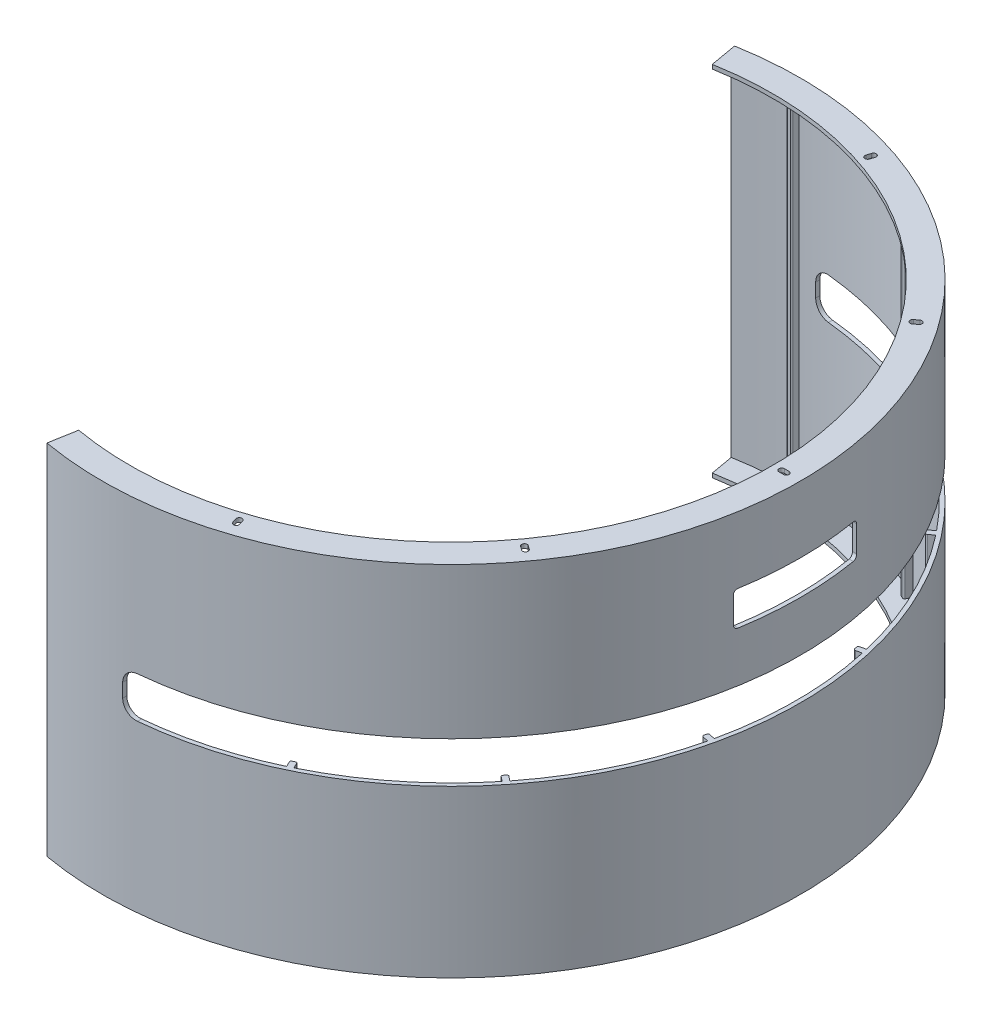
SolidWorks part; units mm, degrees
ref_plane "Front Plane" through (0, 0, 0) normal (0, 0, 1) x (1, 0, 0)
ref_plane "Top Plane" through (0, 0, 0) normal (0, 1, 0) x (1, 0, 0)
ref_plane "Right Plane" through (0, 0, 0) normal (1, 0, 0) x (0, 0, -1)
sketch "Sketch3" plane through (0, 0, 0) normal (0, 1, 0) x (1, 0, 0)
  line L0 (0, -251.5) -> (0, 251.5)
  line L1 (-44.1935, 250.6336) -> (-43.6725, 247.6791)
  line L2 (-43.6725, -247.6791) -> (-44.1935, -250.6336)
  arc A0 (0, 251.5) -> (0, -251.5) centre (0, 0) cw
  arc A1 (0, 251.5) -> (-43.6725, 247.6791) centre (0, 0) ccw
  arc A2 (0, -251.5) -> (-43.6725, -247.6791) centre (0, 0) cw
  arc A3 (0, 254.5) -> (0, -254.5) centre (0, 0) cw
  arc A4 (0, 254.5) -> (-44.1935, 250.6336) centre (0, 0) ccw
  arc A5 (0, -254.5) -> (-44.1935, -250.6336) centre (0, 0) cw
  point P4 (0, 0)
  dimension "D1" = 503
  dimension "D2" = 3
  dimension "D3" = 3
  dimension "D4" = 3
extrude "Boss-Extrude1" add sketch "Sketch3" along normal blind 255 contours A5 A3 A4 L1 A1 A0 A2 L2 region at (252.0902, 0, 0)
sketch "Sketch6" plane through (0, 255, 0) normal (0, 1, 0) x (1, 0, 0)
  line L0 (0, -256) -> (0, 256)
  line L1 (-2, 253.0819) -> (-2, 247.0819)
  line L2 (-1, 246.0819) -> (1, 246.0819)
  line L3 (2, 247.0819) -> (2, 253.0819)
  line L4 (-2, 253.0819) -> (2, 253.0819)
  line L54 (108.0062, 228.8867) -> (105.4029, 223.4809)
  line L55 (105.87, 222.146) -> (107.6719, 221.2783)
  line L56 (109.0068, 221.7454) -> (111.6101, 227.1512)
  line L57 (108.0062, 228.8867) -> (111.6101, 227.1512)
  line L58 (196.6204, 159.3577) -> (191.9294, 155.6167)
  line L59 (191.7711, 154.2114) -> (193.0181, 152.6477)
  line L60 (194.4234, 152.4894) -> (199.1144, 156.2303)
  line L61 (196.6204, 159.3577) -> (199.1144, 156.2303)
  line L62 (246.2916, 58.2659) -> (240.442, 56.9308)
  line L63 (239.6896, 55.7333) -> (240.1347, 53.7835)
  line L64 (241.3321, 53.031) -> (247.1817, 54.3662)
  line L65 (246.2916, 58.2659) -> (247.1817, 54.3662)
  line L66 (247.1817, -54.3662) -> (241.3321, -53.031)
  line L67 (240.1347, -53.7835) -> (239.6896, -55.7333)
  line L68 (240.442, -56.9308) -> (246.2916, -58.2659)
  line L69 (247.1817, -54.3662) -> (246.2916, -58.2659)
  line L70 (199.1144, -156.2303) -> (194.4234, -152.4894)
  line L71 (193.0181, -152.6477) -> (191.7711, -154.2114)
  line L72 (191.9294, -155.6167) -> (196.6204, -159.3577)
  line L73 (199.1144, -156.2303) -> (196.6204, -159.3577)
  line L74 (111.6101, -227.1512) -> (109.0068, -221.7454)
  line L75 (107.6719, -221.2783) -> (105.87, -222.146)
  line L76 (105.4029, -223.4809) -> (108.0062, -228.8867)
  line L77 (111.6101, -227.1512) -> (108.0062, -228.8867)
  line L78 (2, -253.0819) -> (2, -247.0819)
  line L79 (1, -246.0819) -> (-1, -246.0819)
  line L80 (-2, -247.0819) -> (-2, -253.0819)
  line L81 (2, -253.0819) -> (-2, -253.0819)
  arc A2 (2, 247.0819) -> (1, 246.0819) centre (1, 247.0819) cw
  arc A3 (-2, 247.0819) -> (-1, 246.0819) centre (-1, 247.0819) ccw
  arc A26 (109.0068, 221.7454) -> (107.6719, 221.2783) centre (108.1058, 222.1792) cw
  arc A27 (105.4029, 223.4809) -> (105.87, 222.146) centre (106.3039, 223.047) ccw
  arc A28 (194.4234, 152.4894) -> (193.0181, 152.6477) centre (193.7999, 153.2712) cw
  arc A29 (191.9294, 155.6167) -> (191.7711, 154.2114) centre (192.5529, 154.8349) ccw
  arc A30 (241.3321, 53.031) -> (240.1347, 53.7835) centre (241.1096, 54.006) cw
  arc A31 (240.442, 56.9308) -> (239.6896, 55.7333) centre (240.6645, 55.9558) ccw
  arc A32 (240.442, -56.9308) -> (239.6896, -55.7333) centre (240.6645, -55.9558) cw
  arc A33 (241.3321, -53.031) -> (240.1347, -53.7835) centre (241.1096, -54.006) ccw
  arc A34 (191.9294, -155.6167) -> (191.7711, -154.2114) centre (192.5529, -154.8349) cw
  arc A35 (194.4234, -152.4894) -> (193.0181, -152.6477) centre (193.7999, -153.2712) ccw
  arc A36 (105.4029, -223.4809) -> (105.87, -222.146) centre (106.3039, -223.047) cw
  arc A37 (109.0068, -221.7454) -> (107.6719, -221.2783) centre (108.1058, -222.1792) ccw
  arc A38 (-2, -247.0819) -> (-1, -246.0819) centre (-1, -247.0819) cw
  arc A39 (2, -247.0819) -> (1, -246.0819) centre (1, -247.0819) ccw
  point P9 (0, 0)
  point P19 (2, 246.0819)
  point P22 (-2, 246.0819)
  point P23 (0, 246.0819)
  point P59 (0, 0)
  point P68 (0, 0)
  point P76 (0, 0)
  dimension "D3" = 1
  dimension "D1" = 7
  dimension "D2" = 4
  dimension "D4" = 0
  dimension "D5" = 7
  dimension "D6" = 256
  dimension "D7" = 8
extrude "Boss-Extrude2" add sketch "Sketch6" against normal blind 255 separate body contours L3 L4 L1 A3 L2 A2 | L56 L57 L54 A27 L55 A26 | L60 L61 L58 A29 L59 A28 | L64 L65 L62 A31 L63 A30 | L68 L69 L66 A33 L67 A32 | L72 L73 L70 A35 L71 A34 | L76 L77 L74 A37 L75 A36 | L78 A39 L79 A38 L80 L81
combine bodies "Combine2" operation type add bodies to combine 109 101 115 116 117 118 119 120 121
sketch "Sketch4" plane through (0, 0, 0) normal (0, 0, 1) x (1, 0, 0)
  line L0 (254.5, 0) -> (254.5, 255) construction
  line L1 (494.5, 118) -> (14.5, 118)
  line L2 (494.5, 118) -> (494.5, 148)
  line L3 (494.5, 148) -> (14.5, 148)
  line L4 (14.5, 118) -> (14.5, 148)
  line L5 (494.5, 118) -> (14.5, 148) construction
  line L6 (494.5, 148) -> (14.5, 118) construction
  line L7 (-44.1935, 0) -> (254.5, 0) construction
  point P0 (254.5, 133)
  dimension "D1" = 30
  dimension "D2" = 118
  dimension "D3" = 480
extrude "Cut-Extrude2" cut sketch "Sketch4" against normal mid plane 953
fillet "Fillet2" radius 10 4 edges at (14.5, 148, -252.5841) (14.5, 118, -252.5841) (14.5, 118, 252.5841) (14.5, 148, 252.5841)
sketch "Sketch7" plane through (0, 255, 0) normal (0, 1, 0) x (1, 0, 0)
  line L0 (-44.1935, 250.6336) -> (-40.7205, 230.9374)
  line L1 (-44.1935, -250.6336) -> (-40.7205, -230.9374)
  arc A0 (-40.7205, 230.9374) -> (-40.7205, -230.9374) centre (0, 0) cw
  arc A2 (-44.1935, 250.6336) -> (-44.1935, -250.6336) centre (0, 0) cw
  arc A3 (-44.1935, -250.6336) -> (-44.1935, 250.6336) centre (0, 0) ccw construction
extrude "Boss-Extrude3" add sketch "Sketch7" along normal blind 3 contours A2 L0 A0 L1 region at (248.5983, 255, 0)
sketch "Sketch8" plane through (0, 255, 0) normal (0, -1, 0) x (1, 0, 0)
  line L0 (240.8, 0) -> (244.2, 0) construction
  line L1 (240.8, 2) -> (244.2, 2)
  line L2 (240.8, -2) -> (244.2, -2)
  line L3 (194.8113, -141.5387) -> (197.562, -143.5372) construction
  line L12 (195.9869, -139.9207) -> (198.7375, -141.9191)
  line L21 (193.6357, -143.1567) -> (196.3864, -145.1552)
  line L24 (74.4113, -229.0144) -> (75.462, -232.248) construction
  line L27 (76.3134, -228.3964) -> (77.3641, -231.63)
  line L28 (72.5092, -229.6324) -> (73.5598, -232.866)
  line L29 (-74.4113, -229.0144) -> (-75.462, -232.248) construction
  line L30 (-72.5092, -229.6324) -> (-73.5598, -232.866)
  line L31 (-76.3134, -228.3964) -> (-77.3641, -231.63)
  line L32 (-194.8113, -141.5387) -> (-197.562, -143.5372) construction
  line L33 (-193.6357, -143.1567) -> (-196.3864, -145.1552)
  line L34 (-195.9869, -139.9207) -> (-198.7375, -141.9191)
  line L35 (-240.8, 0) -> (-244.2, 0) construction
  line L36 (-240.8, -2) -> (-244.2, -2)
  line L37 (-240.8, 2) -> (-244.2, 2)
  line L38 (-194.8113, 141.5387) -> (-197.562, 143.5372) construction
  line L39 (-195.9869, 139.9207) -> (-198.7375, 141.9191)
  line L40 (-193.6357, 143.1567) -> (-196.3864, 145.1552)
  line L41 (-74.4113, 229.0144) -> (-75.462, 232.248) construction
  line L42 (-76.3134, 228.3964) -> (-77.3641, 231.63)
  line L43 (-72.5092, 229.6324) -> (-73.5598, 232.866)
  line L44 (74.4113, 229.0144) -> (75.462, 232.248) construction
  line L45 (72.5092, 229.6324) -> (73.5598, 232.866)
  line L46 (76.3134, 228.3964) -> (77.3641, 231.63)
  line L47 (194.8113, 141.5387) -> (197.562, 143.5372) construction
  line L48 (193.6357, 143.1567) -> (196.3864, 145.1552)
  line L49 (195.9869, 139.9207) -> (198.7375, 141.9191)
  circle A1 centre (242.5, 0) radius 1.7 construction
  arc A2 (240.8, 2) -> (240.8, -2) centre (240.8, 0) ccw
  arc A3 (244.2, -2) -> (244.2, 2) centre (244.2, 0) ccw
  arc A24 (195.9869, -139.9207) -> (193.6357, -143.1567) centre (194.8113, -141.5387) ccw
  arc A25 (196.3864, -145.1552) -> (198.7375, -141.9191) centre (197.562, -143.5372) ccw
  arc A26 (76.3134, -228.3964) -> (72.5092, -229.6324) centre (74.4113, -229.0144) ccw
  arc A27 (73.5598, -232.866) -> (77.3641, -231.63) centre (75.462, -232.248) ccw
  arc A28 (-72.5092, -229.6324) -> (-76.3134, -228.3964) centre (-74.4113, -229.0144) ccw
  arc A29 (-77.3641, -231.63) -> (-73.5598, -232.866) centre (-75.462, -232.248) ccw
  arc A30 (-193.6357, -143.1567) -> (-195.9869, -139.9207) centre (-194.8113, -141.5387) ccw
  arc A31 (-198.7375, -141.9191) -> (-196.3864, -145.1552) centre (-197.562, -143.5372) ccw
  arc A32 (-240.8, -2) -> (-240.8, 2) centre (-240.8, 0) ccw
  arc A33 (-244.2, 2) -> (-244.2, -2) centre (-244.2, 0) ccw
  arc A34 (-195.9869, 139.9207) -> (-193.6357, 143.1567) centre (-194.8113, 141.5387) ccw
  arc A35 (-196.3864, 145.1552) -> (-198.7375, 141.9191) centre (-197.562, 143.5372) ccw
  arc A36 (-76.3134, 228.3964) -> (-72.5092, 229.6324) centre (-74.4113, 229.0144) ccw
  arc A37 (-73.5598, 232.866) -> (-77.3641, 231.63) centre (-75.462, 232.248) ccw
  arc A38 (72.5092, 229.6324) -> (76.3134, 228.3964) centre (74.4113, 229.0144) ccw
  arc A39 (77.3641, 231.63) -> (73.5598, 232.866) centre (75.462, 232.248) ccw
  arc A40 (193.6357, 143.1567) -> (195.9869, 139.9207) centre (194.8113, 141.5387) ccw
  arc A41 (198.7375, 141.9191) -> (196.3864, 145.1552) centre (197.562, 143.5372) ccw
  point P6 (242.5, 0)
  point P16 (196.1866, -142.5379)
  point P23 (74.9366, -230.6312)
  point P28 (0, 0)
  point P31 (-74.9366, -230.6312)
  point P35 (0, 0)
  point P39 (-196.1866, -142.5379)
  point P44 (0, 0)
  point P47 (-242.5, 0)
  point P54 (-196.1866, 142.5379)
  point P57 (0, 0)
  point P62 (-74.9366, 230.6312)
  point P69 (74.9366, 230.6312)
  point P76 (196.1866, 142.5379)
  point P81 (0, 0)
  dimension "D1" = 2
extrude "Cut-Extrude3" cut sketch "Sketch8" against normal blind 5
pattern_linear "LPattern1" count 2 spacing 258 along (0, -1, 0) of "Boss-Extrude3"
pattern_linear "LPattern2" count 2 spacing 258 along (0, -1, 0) of "Cut-Extrude3"
sketch "Sketch9" plane through (0, 0, 0) normal (0, 0, 1) x (1, 0, 0)
  line L0 (254.5, 148) -> (254.5, 258) construction
  line L1 (268.0504, 184.5) -> (240.9496, 184.5)
  line L2 (268.0504, 184.5) -> (268.0504, 209.5)
  line L3 (268.0504, 209.5) -> (240.9496, 209.5)
  line L4 (240.9496, 184.5) -> (240.9496, 209.5)
  line L5 (268.0504, 184.5) -> (240.9496, 209.5) construction
  line L6 (268.0504, 209.5) -> (240.9496, 184.5) construction
  point P0 (254.5, 197)
  dimension "D1" = 25
  dimension "D2" = 200
extrude "Cut-Extrude4" cut sketch "Sketch9" against normal mid plane 90
fillet "Fillet3" radius 3 4 edges at (248.9657, 209.5, 45) (248.9657, 184.5, 45) (248.9657, 184.5, -45) (248.9657, 209.5, -45)
